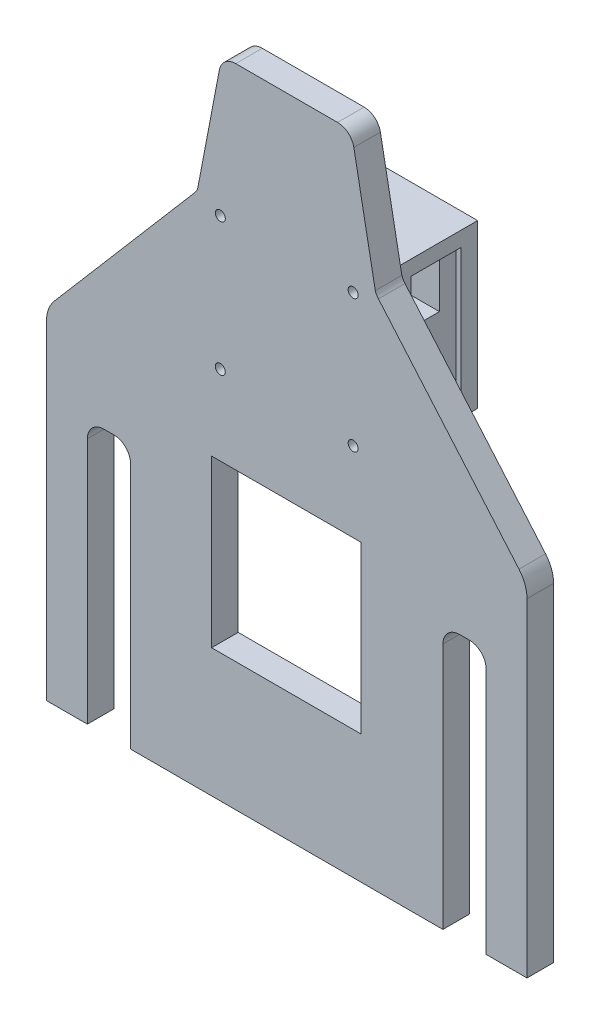
SolidWorks part; units mm, degrees
ref_plane "Front Plane" through (0, 0, 0) normal (0, 0, 1) x (1, 0, 0)
ref_plane "Top Plane" through (0, 0, 0) normal (0, 1, 0) x (1, 0, 0)
ref_plane "Right Plane" through (0, 0, 0) normal (1, 0, 0) x (0, 0, -1)
sketch "Sketch1" plane through (0, 0, 0) normal (0, 0, 1) x (1, 0, 0)
  line L4 (70, 309.9858) -> (85.2992, 309.9858)
  line L6 (43.2101, 271.7903) -> (49.7246, 305.9232)
  line L7 (42.2614, 270.1156) -> (0.0495, 220.7861)
  line L8 (0.0495, 220.7861) -> (42.9, 220.7861) construction
  line L9 (42.9, 220.7861) -> (42.9, 270.8599) construction
  line L10 (96.9829, 220.8599) -> (96.9829, 270.8599) construction
  line L11 (112.4871, 25.7747) -> (89.3829, 25.7747) construction
  line L12 (27.5129, 25.7747) -> (50.5, 25.7747) construction
  line L13 (25.2828, 25.7823) -> (2.6386, 25.8599)
  line L14 (96.6727, 271.7903) -> (90.212, 305.9159)
  line L15 (70, 329.5221) -> (70, -78.2612) construction
  line L18 (50.5, 25.7747) -> (50.5, 0) construction
  line L19 (70, 309.9858) -> (54.636, 309.9858)
  line L20 (135.9829, 220.8599) -> (96.9829, 220.8599) construction
  line L21 (139.9505, 220.7861) -> (135.9829, 220.8599) construction
  line L25 (89.3829, 25.7747) -> (89.3829, 0) construction
  line L27 (89.3829, 0) -> (50.5, 0)
  line L28 (15.2188, 54.8072) -> (17.7021, 54.8072)
  line L35 (125.0395, 54.8072) -> (122.0396, 54.8072)
  line L36 (122.0396, 194.8072) -> (125.0395, 194.8072)
  line L37 (117.0396, 59.8072) -> (117.0396, 189.8072)
  line L38 (130.0395, 189.8072) -> (130.0395, 59.8072)
  line L39 (142.3614, 214.274) -> (142.3614, 30.8599)
  line L40 (97.6215, 270.1156) -> (139.9505, 220.7861)
  line L41 (-2.3614, 214.274) -> (-2.3614, 30.8599)
  line L42 (9.9605, 189.8072) -> (9.9605, 60.0656)
  line L43 (22.9604, 60.0656) -> (22.9604, 189.8072)
  line L44 (17.9604, 194.8072) -> (14.9605, 194.8072)
  line L45 (28.9972, 24.1103) -> (50.5, 0)
  line L46 (114.7172, 25.7823) -> (137.3614, 25.8599)
  line L47 (89.3829, 0) -> (111.0028, 24.1103)
  arc A1 (42.2614, 270.1156) -> (43.2101, 271.7903) centre (38.4667, 273.3715) ccw
  arc A5 (97.6215, 270.1156) -> (96.6727, 271.7903) centre (101.4161, 273.3715) cw
  arc A8 (137.3614, 25.8599) -> (142.3614, 30.8599) centre (137.3614, 30.8599) ccw
  arc A9 (2.6386, 25.8599) -> (-2.3614, 30.8599) centre (2.6386, 30.8599) cw
  arc A10 (49.7246, 305.9232) -> (54.636, 309.9858) centre (54.636, 304.9858) cw
  arc A11 (85.2992, 309.9858) -> (90.212, 305.9159) centre (85.2992, 304.9858) cw
  arc A12 (139.9505, 220.7861) -> (142.3614, 214.274) centre (132.3614, 214.274) cw
  arc A13 (0.0495, 220.7861) -> (-2.3614, 214.274) centre (7.6386, 214.274) ccw
  arc A14 (25.2828, 25.7823) -> (28.9972, 24.1103) centre (25.2657, 20.7823) cw
  arc A15 (114.7172, 25.7823) -> (111.0028, 24.1103) centre (114.7343, 20.7823) ccw
  arc A16 (17.9604, 194.8072) -> (22.9604, 189.8072) centre (17.9604, 189.8072) cw
  arc A17 (9.9605, 189.8072) -> (14.9605, 194.8072) centre (14.9605, 189.8072) cw
  arc A18 (125.0395, 54.8072) -> (130.0395, 59.8072) centre (125.0395, 59.8072) ccw
  arc A19 (122.0396, 54.8072) -> (117.0396, 59.8072) centre (122.0396, 59.8072) cw
  arc A20 (125.0395, 194.8072) -> (130.0395, 189.8072) centre (125.0395, 189.8072) cw
  arc A21 (117.0396, 189.8072) -> (122.0396, 194.8072) centre (122.0396, 189.8072) cw
  arc A22 (17.7021, 54.8072) -> (22.9604, 60.0656) centre (17.7021, 60.0656) ccw
  arc A23 (15.2188, 54.8072) -> (9.9605, 60.0656) centre (15.2188, 60.0656) cw
  point P18 (22.9604, 194.8072)
  point P51 (9.9605, 194.8072)
  point P57 (130.0395, 54.8072)
  point P61 (117.0396, 54.8072)
  point P67 (130.0395, 194.8072)
  point P70 (117.0396, 194.8072)
  point P77 (22.9604, 54.8072)
  point P80 (9.9605, 54.8072)
  dimension "D1" = 5
  dimension "D2" = 5
  dimension "D3" = 5
  dimension "D4" = 10
  dimension "D5" = 5
  dimension "D6" = 5
  dimension "D7" = 5.2583
extrude "Boss-Extrude1" add sketch "Sketch1" along normal blind 8
sketch "Sketch2" plane through (0, 0, 8) normal (0, 0, 1) x (1, 0, 0)
  line L2 (92.3829, 204.0089) -> (47.3829, 204.0089)
  line L8 (47.3829, 204.0089) -> (47.3829, 154.0089)
  line L9 (47.3829, 154.0089) -> (92.3829, 154.0089)
  line L10 (92.3829, 204.0089) -> (92.3829, 154.0089)
extrude "Cut-Extrude1" cut sketch "Sketch2" against normal through all contours L10 L2 L8 L9 region at (69.8829, 179.0089, 8)
sketch "Sketch3" plane through (0, 0, 0) normal (0, 0, -1) x (-1, 0, 0)
  line L1 (-142.3614, 115.3599) -> (2.3614, 115.3599)
  line L3 (-142.3614, 30.8599) -> (-142.3614, 214.274) construction
  line L6 (2.3614, 214.274) -> (2.3614, 30.8599) construction
split "Split1" trim tools "Sketch3" bodies to split 102 resulting bodies 104 108
ref_plane "Plane4" through (0, 115.3599, 0) normal (0, 1, 0) x (1, 0, 0)
sketch "Sketch4" plane through (0, 115.3599, 0) normal (0, -1, 0) x (-1, 0, 0)
  line L0 (-3.7995, -8) -> (-3.7995, -4)
  line L2 (2.3614, -8) -> (-9.9605, -8) construction
  circle A1 centre (-70, -4) radius 2.5
  circle A2 centre (-40, -4) radius 2.5
  circle A3 centre (-100, -4) radius 2.5
  circle A5 centre (-137.3614, -4) radius 2.5
  circle A6 centre (-3.7995, -4) radius 2.5
sketch "Sketch5" plane through (0, 115.3599, -115.3599) normal (0, -1, 0) x (1, 0, 0)
  circle A1 centre (70, 119.3599) radius 2.5
  circle A2 centre (100, 119.3599) radius 2.5
  circle A3 centre (40, 119.3599) radius 2.5
  circle A5 centre (2.6386, 119.3599) radius 2.5
  circle A6 centre (137.3614, 119.3599) radius 2.5
extrude "Cut-Extrude6" cut sketch "Sketch5" along direction (0, -1, 0) on the side of the normal blind 5.2 contours A5 | A3 | A1
extrude "Cut-Extrude7" cut sketch "Sketch4" against normal blind 10 contours A2 | A6 | A1 | A3 | A5 region at (70, 115.3599, 4) region at (40, 115.3599, 4) region at (100, 115.3599, 4) region at (2.0817, 115.3599, 5.7178)
delete or keep bodies "Body-Delete/Keep 3" type delete bodies bodies 106
sketch "Sketch6" plane through (0, 0, 8) normal (0, 0, 1) x (1, 0, 0)
  circle A0 centre (50.0001, 267.9803) radius 1.5
  circle A1 centre (90.0001, 267.9803) radius 1.5
  circle A2 centre (90.0001, 227.9803) radius 1.5
  circle A3 centre (50.0001, 227.9803) radius 1.5
extrude "Cut-Extrude8" cut sketch "Sketch6" against normal through all
sketch "Sketch7" plane through (0, 0, 0) normal (0, 0, -1) x (-1, 0, 0)
  line L10 (-94.5001, 223.4803) -> (-94.5001, 272.4803)
  line L11 (-47.0001, 270.9803) -> (-47.0001, 252.9803)
  line L12 (-45.5001, 272.4803) -> (-45.5001, 223.4803)
  line L13 (-45.5001, 223.4803) -> (-94.5001, 223.4803)
  line L14 (-93.0001, 270.9803) -> (-75.0001, 270.9803)
  line L15 (-93.0001, 224.9803) -> (-75.0001, 224.9803)
  line L16 (-93.0001, 224.9803) -> (-93.0001, 242.9803)
  line L18 (-65.0001, 270.9803) -> (-65.0001, 252.9803)
  line L19 (-65.0001, 224.9803) -> (-47.0001, 224.9803)
  line L20 (-45.5001, 272.4803) -> (-94.5001, 272.4803)
  line L21 (-75.0001, 270.9803) -> (-75.0001, 252.9803)
  line L22 (-47.0001, 252.9803) -> (-65.0001, 252.9803)
  line L23 (-47.0001, 242.9803) -> (-47.0001, 224.9803)
  line L24 (-93.0001, 242.9803) -> (-75.0001, 242.9803)
  line L25 (-65.0001, 270.9803) -> (-47.0001, 270.9803)
  line L26 (-75.0001, 252.9803) -> (-93.0001, 252.9803)
  line L27 (-65.0001, 242.9803) -> (-47.0001, 242.9803)
  line L28 (-65.0001, 242.9803) -> (-65.0001, 224.9803)
  line L29 (-75.0001, 242.9803) -> (-75.0001, 224.9803)
  line L30 (-93.0001, 252.9803) -> (-93.0001, 270.9803)
extrude "Boss-Extrude2" add sketch "Sketch7" along normal blind 15
sketch "Sketch8" plane through (0, 0, -15) normal (0, 0, -1) x (-1, 0, 0)
  line L0 (-45.5001, 272.4803) -> (-94.5001, 272.4803)
  line L1 (-94.5001, 272.4803) -> (-94.5001, 223.4803)
  line L2 (-94.5001, 223.4803) -> (-45.5001, 223.4803)
  line L3 (-94.5001, 223.4803) -> (-45.5001, 223.4803) construction
  line L4 (-94.5001, 223.4803) -> (-45.5001, 223.4803) construction
  line L5 (-45.5001, 223.4803) -> (-45.5001, 272.4803)
  circle A0 centre (-50.0001, 267.9803) radius 1.5
  circle A1 centre (-90.0001, 267.9803) radius 1.5
  circle A2 centre (-50.0001, 227.9803) radius 1.5
  circle A3 centre (-90.0001, 227.9803) radius 1.5
extrude "Boss-Extrude3" add sketch "Sketch8" along normal blind 10
sketch "Sketch9" plane through (45.5001, 0, 0) normal (-1, 0, 0) x (0, 0, 1)
  line L2 (-20, 267.9803) -> (-20, 227.9803)
  line L3 (-20, 267.9803) -> (-5, 267.9803)
  line L6 (-5, 267.9803) -> (-5, 227.9803)
  line L7 (-5, 227.9803) -> (-20, 227.9803)
extrude "Cut-Extrude9" cut sketch "Sketch9" against normal blind 1.5
sketch "Sketch11" plane through (94.5001, 0, 0) normal (1, 0, 0) x (0, 0, -1)
  line L3 (20, 267.9803) -> (20, 227.9803)
  line L4 (20, 227.9803) -> (5, 227.9803)
  line L5 (5, 227.9803) -> (5, 267.9803)
  line L6 (5, 267.9803) -> (20, 267.9803)
extrude "Cut-Extrude10" cut sketch "Sketch11" against normal blind 1.5
